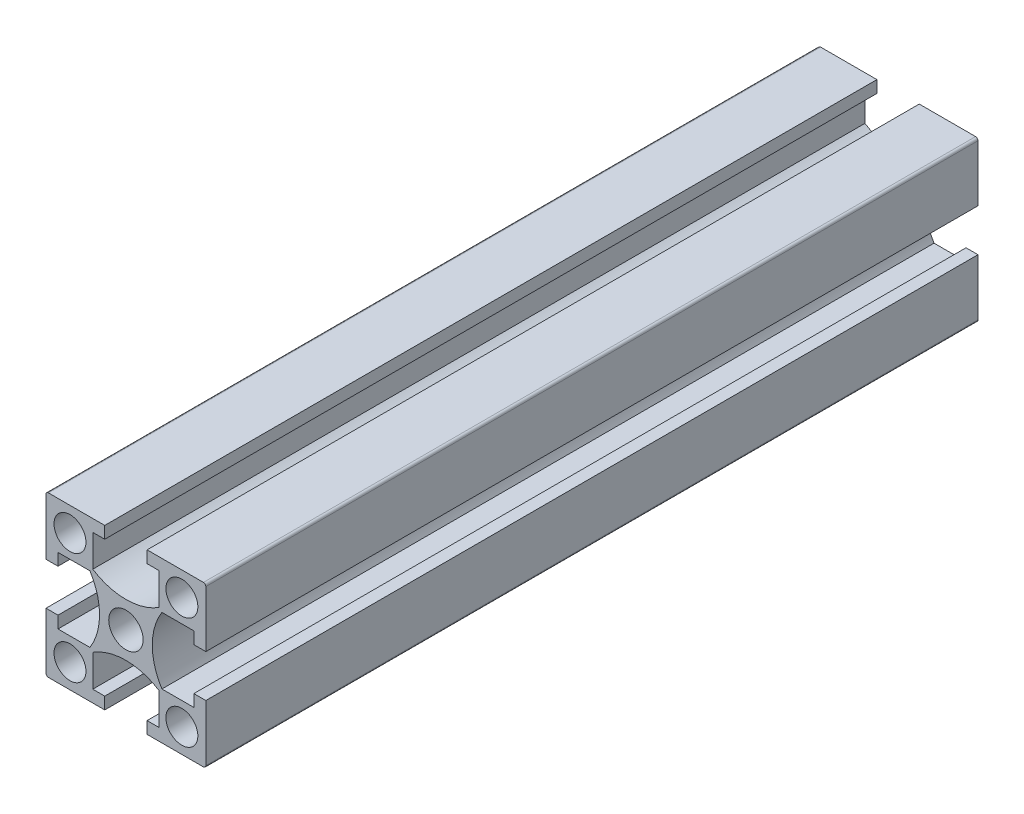
SolidWorks part; units mm, degrees
material "3.0255 (EN-AW 1350A)"
ref_plane "정면" through (0, 0, 0) normal (0, 0, 1) x (1, 0, 0)
ref_plane "윗면" through (0, 0, 0) normal (0, 1, 0) x (1, 0, 0)
ref_plane "우측면" through (0, 0, 0) normal (1, 0, 0) x (0, 0, -1)
sketch "스케치1" plane through (0, 0, 0) normal (0, 0, 1) x (1, 0, 0)
  line L0 (0, 32.0265) -> (0, -31.6588) construction
  line L1 (-10, 10) -> (-10, -10)
  line L2 (-10, 10) -> (10, 10)
  line L3 (-10, 2.65) -> (-8.5, 2.65)
  line L4 (13.6618, 0) -> (-11.6993, 0) construction
  line L5 (-8.5, 2.65) -> (-8.5, 4.15)
  line L6 (-8.5, 4.15) -> (-4.5032, 4.15)
  line L7 (-10, -2.65) -> (-8.5, -2.65)
  line L8 (-8.5, -2.65) -> (-8.5, -4.15)
  line L9 (-8.5, -4.15) -> (-4.5032, -4.15)
  line L10 (-10, -10) -> (10, -10)
  line L11 (10, 10) -> (10, -10)
  circle A0 centre (-7, 7) radius 2
  circle A1 centre (-7, -7) radius 2
  arc A2 (-4.5032, 4.15) -> (-4.5032, -4.15) centre (-11.0587, 0) cw
  circle A3 centre (0, 0) radius 2.15
  circle A4 centre (7, 7) radius 2
  circle A5 centre (7, -7) radius 2
  point P21 (-10, 0)
  point P23 (-3.3, 0)
  point P31 (0, -10)
  point P32 (0, 10)
  dimension "D3" = 4
  dimension "D9" = 6.7
  dimension "D10" = 4.3
  dimension "D11" = 7.7587
  dimension "D1" = 20
  dimension "D2" = 20
  dimension "D4" = 14
  dimension "D5" = 14
  dimension "D6" = 5.3
  dimension "D7" = 8.3
  dimension "D8" = 1.5
extrude "보스-돌출1" add sketch "스케치1" along normal blind 293 contours A0 | A4 | A3 | A5 | A1 | A2 L6 L5 L3 L1 L7 L8 L9 | L2 L11 L10 L1 region at (-6.6069, 0, 0) region at (-7, 7, 0) region at (-7, -7, 0) region at (0, 0, 0) region at (7, 7, 0) region at (7, -7, 0)
extrude "컷-돌출1" cut sketch "스케치1<3>" along normal up to next contours A2 L6 L5 L3 L1 L7 L8 L9 region at (-6.6069, 0, 0)
sketch "스케치1<3>" plane through (0, 0, 0) normal (0, 0, 1) x (1, 0, 0) same geometry as "스케치1"
pattern_circular "원형 패턴1" count 4 over 360 about axis through (0, 0, 293) along (0, 0, -1) of "컷-돌출1" reverse direction yes
fillet "필렛1" radius 0.3 4 edges at (10, -10, 146.5) (-10, -10, 146.5) (-10, 10, 146.5) (10, 10, 146.5)
sketch "스케치2" plane through (0, 0, 0) normal (1, 0, 0) x (0, 0, -1)
  circle A0 centre (-25, 0) radius 2.5
  dimension "D1" = 5
  dimension "D2" = 25
extrude "컷-돌출2" cut sketch "스케치2" against normal through all both and the other way through all
sketch "스케치4" plane through (0, 10, 0) normal (0, 1, 0) x (1, 0, 0)
  line L0 (0, -11) -> (0, 11) construction
  line L3 (-2.65, -106.62) -> (2.65, -106.62) construction
  line L4 (-2.65, -293) -> (-2.65, 0) construction
  line L5 (2.65, -293) -> (2.65, 0) construction
  line L6 (2.65, 0) -> (9.7, 0) construction
  circle A1 centre (0, -282) radius 2.5
  circle A2 centre (0, -127.62) radius 2.5
  dimension "D2" = 282
  dimension "D3" = 106.62
  dimension "D4" = 21
extrude "컷-돌출3" cut sketch "스케치4" against normal through all
sketch "스케치6" plane through (0, 10, 0) normal (0, 1, 0) x (1, 0, 0)
  line L0 (0, -11) -> (0, 11) construction
  line L1 (4.15, 0) -> (-4.15, 0) construction
  line L3 (-9.7, 0) -> (-2.65, 0) construction
  circle A0 centre (0, -236.9) radius 2.15
  circle A1 centre (0, -184.9) radius 2.15
  circle A2 centre (0, -10.15) radius 1.9797
  circle A3 centre (0, -62.15) radius 2.15
  dimension "D1" = 184.9
  dimension "D2" = 236.9
  dimension "D4" = 52
  dimension "D3" = 10.15
extrude "컷-돌출4" cut sketch "스케치6" against normal through all
sketch "스케치7" plane through (0, 10, 0) normal (0, 1, 0) x (1, 0, 0)
  line L0 (-10, -96.62) -> (10, -96.62)
  line L1 (-10, -293) -> (-10, 0) construction
  line L2 (10, 0) -> (10, -293) construction
  line L3 (-10, -96.62) -> (-10, -293)
  line L4 (-10, -293) -> (10, -293)
  line L5 (10, -293) -> (10, -96.62)
extrude "컷-돌출5" cut sketch "스케치7" against normal through all
